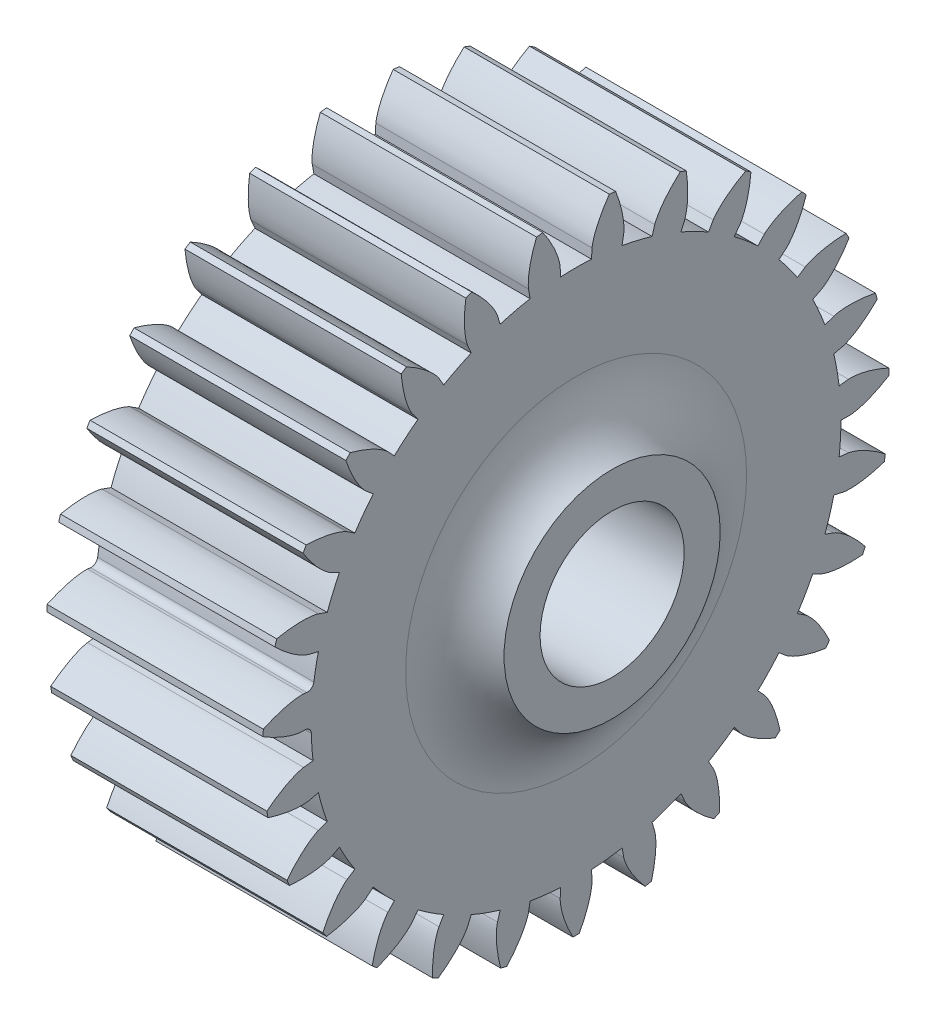
SolidWorks part; units mm, degrees
ref_plane "Front Plane" through (0, 0, 0) normal (1, 0, 0) x (0, 1, 0)
ref_plane "Top Plane" through (0, 0, 0) normal (0, 0, 1) x (0, 1, 0)
ref_plane "Right Plane" through (0, 0, 0) normal (0, 1, 0) x (-1, 0, 0)
sketch "Sketch3" plane through (0, 0, 0) normal (1, 0, 0) x (0, 1, 0)
  circle A0 centre (0, 0) radius 43.5 construction
  circle A1 centre (0, 0) radius 38.06 construction
  circle A2 centre (0, 0) radius 37.5 construction
  circle A3 centre (0, 0) radius 36.75 construction
  dimension "D1" = 87
  dimension "D2" = 76.12
  dimension "D3" = 75
  dimension "D4" = 73.5
sketch "Sketch4" plane through (0, 0, 0) normal (1, 0, 0) x (0, 1, 0)
  line L0 (0, 38.0576) -> (0, 0)
  line L1 (0, 0) -> (2.5268, 43.4266)
  circle A0 centre (0, 0) radius 43.5 construction
  circle A1 centre (0, 0) radius 43.5
  circle A2 centre (0, 0) radius 38.06 construction
  circle A3 centre (0, 0) radius 38.06
  circle A4 centre (0, 0) radius 36.75 construction
  circle A5 centre (0, 0) radius 36.75
  spline S0 degree 4 poles (0, 38.0576) (0.0023, 38.127) (0.0159, 38.3213) (0.0698, 38.6862) (0.1971, 39.2748) (0.4167, 40.0116) (0.7652, 40.9438) (1.2567, 42.0115) (1.8797, 43.147) (2.8341, 44.6336) (3.9084, 46.0391) (5.0799, 47.3639) (6.5478, 48.8221) (8.0994, 50.192) (10.0221, 51.6684) (12.3471, 53.1882) (14.8204, 54.5614) (17.3808, 55.7643) (19.6832, 56.6719) (21.6932, 57.3491) (23.3881, 57.8476) (24.7555, 58.2075) (26.4752, 58.6094) (28.2114, 58.9482) (29.9539, 59.2254) (31.7116, 59.4421) (33.111, 59.5797) (34.3581, 59.6693) (35.3947, 59.7245) (36.3138, 59.7562) (36.9498, 59.773) (37.7543, 59.781) (38.2563, 59.7814) (38.9695, 59.7754) (39.507, 59.7639) (40.1218, 59.7468) (40.6914, 59.724) (41.2882, 59.6957) (41.8668, 59.6617) (42.3107, 59.6321) (42.6014, 59.6106) (42.748, 59.5993) knots 0 0 0 0 0 0.005377 0.015084 0.028532 0.04661 0.064855 0.092111 0.119476 0.146842 0.201575 0.228941 0.256307 0.307035 0.361767 0.4165 0.471232 0.525964 0.580697 0.608063 0.635429 0.662795 0.690161 0.744894 0.77226 0.799626 0.826992 0.854358 0.868042 0.881725 0.895408 0.909091 0.920455 0.931818 0.943182 0.954545 0.965909 0.977273 0.988636 1 1 1 1 1 construction
  spline S1 degree 4 poles (0, 38.0576) (0.0023, 38.127) (0.0159, 38.3213) (0.0698, 38.6862) (0.1971, 39.2748) (0.4167, 40.0116) (0.7652, 40.9438) (1.2567, 42.0115) (1.8797, 43.147) (2.8341, 44.6336) (3.9084, 46.0391) (5.0799, 47.3639) (6.5478, 48.8221) (8.0994, 50.192) (10.0221, 51.6684) (12.3471, 53.1882) (14.8204, 54.5614) (17.3808, 55.7643) (19.6832, 56.6719) (21.6932, 57.3491) (23.3881, 57.8476) (24.7555, 58.2075) (26.4752, 58.6094) (28.2114, 58.9482) (29.9539, 59.2254) (31.7116, 59.4421) (33.111, 59.5797) (34.3581, 59.6693) (35.3947, 59.7245) (36.3138, 59.7562) (36.9498, 59.773) (37.5799, 59.7793) (37.8969, 59.7807) (38.0576, 59.7807) knots 0 0 0 0 0 0.005377 0.015084 0.028532 0.04661 0.064855 0.092111 0.119476 0.146842 0.201575 0.228941 0.256307 0.307035 0.361767 0.4165 0.471232 0.525964 0.580697 0.608063 0.635429 0.662795 0.690161 0.744894 0.77226 0.799626 0.826992 0.854358 0.868042 0.881725 0.895408 0.909091 0.909091 0.909091 0.909091 0.909091
  dimension "D1" = 3.33
extrude "Boss-Extrude6" add sketch "Sketch4" along normal blind 30 contours L0 A5 L1 | L1 A5 L0 region at (0, 0.7118, 24.4862) region at (0, -0.0066, -0.2286)
extrude "Boss-Extrude7" add sketch "Sketch4<3>" along normal blind 30 contours S1 L0 A5 L1 A3 | S1 A3 L1 A1 region at (0, 1.0868, 37.3878) region at (0, 1.4711, 40.2169)
sketch "Sketch4<3>" plane through (0, 0, 0) normal (1, 0, 0) x (0, 1, 0) same geometry as "Sketch4"
mirror "Mirror6" about plane through (30, 0, 0) normal (0, -0.9983, 0.0581) of "Boss-Extrude7"
fillet "Fillet4" radius 0.9 2 edges at (15, 0, 36.75) (15, 4.2622, 36.502)
pattern_circular "CirPattern11" count 27 over 360 about axis through (30, 0, 0) along (-1, 0, 0) of "Boss-Extrude7"
mirror "Mirror7" about plane through (30, 0, 0) normal (0, -0.8021, -0.5972) of "CirPattern11"
sketch "Sketch5" plane through (30, 0, 0) normal (1, 0, 0) x (0, 0, -1)
  circle A0 centre (0, 0) radius 10
  circle A1 centre (0, 0) radius 15
  dimension "D1" = 20
  dimension "D2" = 30
extrude "Boss-Extrude8" add sketch "Sketch5" along normal blind 5
sketch "Sketch6" plane through (30, 0, 0) normal (1, 0, 0) x (0, 1, 0)
  circle A0 centre (0, 0) radius 10
  dimension "D1" = 20
extrude "Cut-Extrude1" cut sketch "Sketch6" against normal through all
sketch "Sketch7" plane through (0, 0, 0) normal (-1, 0, 0) x (0, 0, 1)
  circle A0 centre (0, 0) radius 10
  circle A1 centre (0, 0) radius 15
  dimension "D1" = 20
  dimension "D2" = 5
extrude "Boss-Extrude9" add sketch "Sketch7" along normal blind 5 contours A1
sketch "Sketch8" plane through (-5, 0, 0) normal (-1, 0, 0) x (0, 0, 1)
  circle A0 centre (0, 0) radius 10
  dimension "D1" = 20
extrude "Cut-Extrude2" cut sketch "Sketch8" against normal through all contours A0
fillet "Fillet5" radius 10 2 edges at (0, 0, -15) (30, 0, -15)
equation "\"N\"= 27"
equation "\"M\"= 3"
equation "\"Pitch\"= \"M\" * \"N\""
equation "\"BaseDia\"= \"Pitch\" * cos ( 20 )"
equation "\"OUTERDIAMETER\"= \"Pitch\" + 2 * \"M\""
equation "\"ROOTDIA\"= \"Pitch\" - 2.5 * \"M\""
equation "\"Cleareance\"= \"Pitch\" - 2 * \"M\""
equation "\"BR\"= \"BaseDia\" / 2"
equation "\"RFR\"= 0.3 * \"M\""
